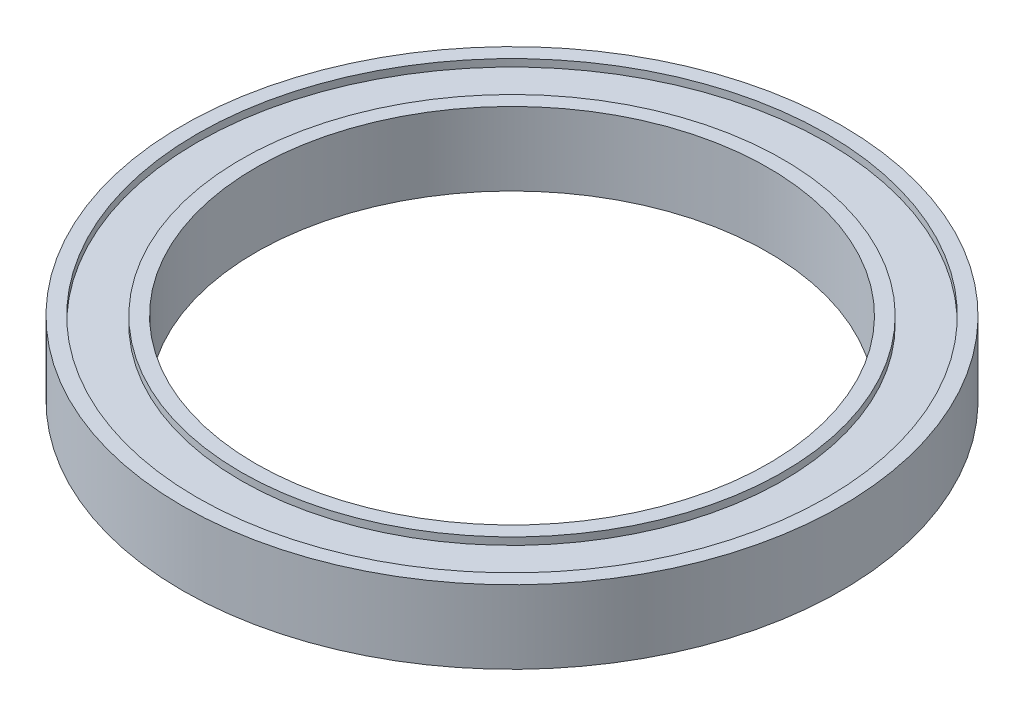
SolidWorks part; units mm, degrees
ref_plane "Front Plane" through (0, 0, 0) normal (0, 0, 1) x (1, 0, 0)
ref_plane "Top Plane" through (0, 0, 0) normal (0, 1, 0) x (1, 0, 0)
ref_plane "Right Plane" through (0, 0, 0) normal (1, 0, 0) x (0, 0, -1)
sketch "Sketch1" plane through (0, 0, 0) normal (0, 1, 0) x (1, 0, 0)
  circle A0 centre (0, 0) radius 35
  circle A1 centre (0, 0) radius 45
  dimension "D1" = 90
  dimension "D2" = 70
extrude "Boss-Extrude1" add sketch "Sketch1" along normal blind 10
sketch "Sketch2" plane through (0, 10, 0) normal (0, 1, 0) x (1, 0, 0)
  circle A2 centre (0, 0) radius 43
  circle A3 centre (0, 0) radius 43
  circle A5 centre (0, 0) radius 37
  circle A6 centre (0, 0) radius 37
  dimension "D1" = 2
  dimension "D2" = 2
extrude "Cut-Extrude1" cut sketch "Sketch2" against normal blind 1
sketch "Sketch3" plane through (0, 0, 0) normal (0, -1, 0) x (1, 0, 0)
  circle A2 centre (0, 0) radius 43
  circle A3 centre (0, 0) radius 43
  circle A5 centre (0, 0) radius 37
  circle A6 centre (0, 0) radius 37
  dimension "D1" = 2
  dimension "D2" = 2
extrude "Cut-Extrude2" cut sketch "Sketch3" against normal blind 1
